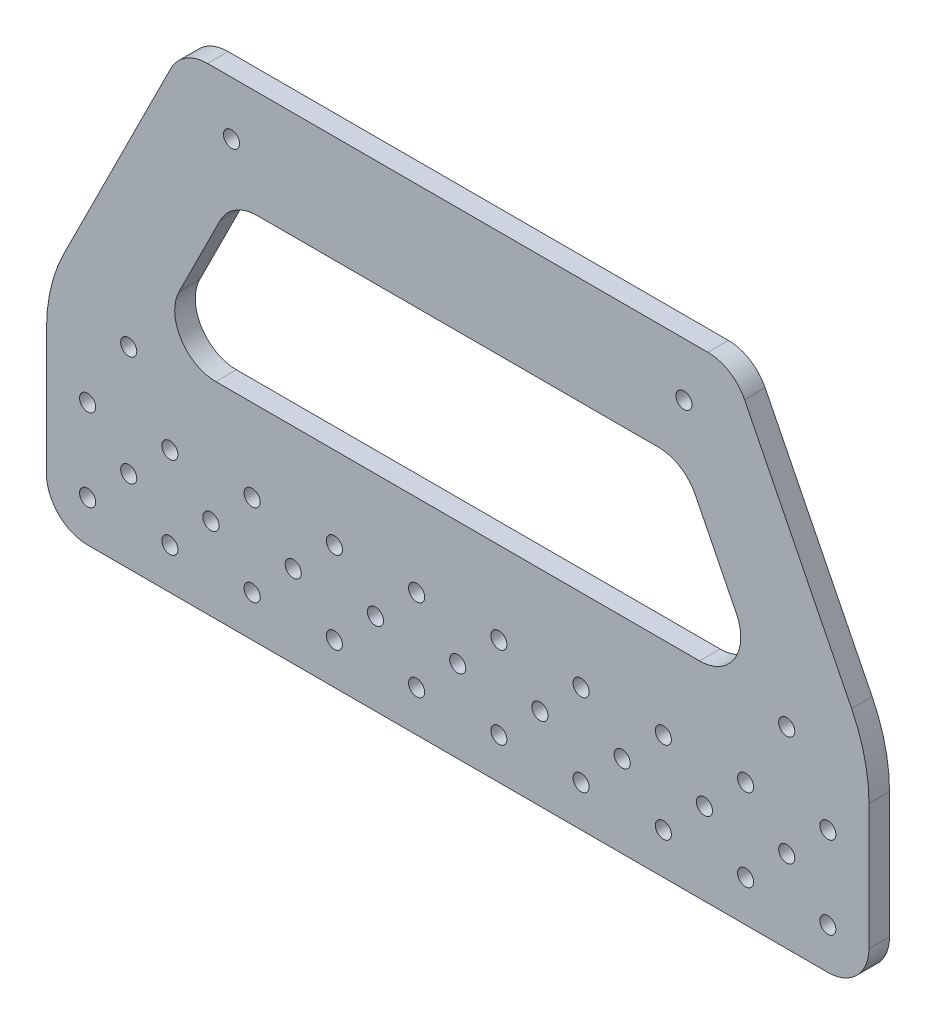
SolidWorks part; units mm, degrees
material "PC High Viscosity"
ref_plane "Front Plane" through (0, 0, 0) normal (0, 0, 1) x (1, 0, 0)
ref_plane "Top Plane" through (0, 0, 0) normal (0, 1, 0) x (1, 0, 0)
ref_plane "Right Plane" through (0, 0, 0) normal (1, 0, 0) x (0, 0, -1)
sketch "Sketch1" plane through (0, 0, 0) normal (0, 0, 1) x (1, 0, 0)
  line L0 (40.9398, 81.8796) -> (53.6398, 107.2796)
  line L1 (12.7, 0) -> (241.3, 0)
  line L2 (0, 12.7) -> (0, 51.5077)
  line L3 (52.299, 63.5) -> (201.701, 63.5)
  line L4 (254, 12.7) -> (254, 51.5077)
  line L5 (57.15, 63.5) -> (196.85, 63.5)
  line L6 (57.15, 63.5) -> (57.15, 114.3) construction
  line L7 (64.999, 114.3) -> (189.001, 114.3)
  line L8 (196.85, 63.5) -> (196.85, 114.3) construction
  line L9 (213.0602, 81.8796) -> (200.3602, 107.2796)
  line L10 (5.3631, 74.2262) -> (38.3998, 140.2996)
  line L11 (49.759, 147.32) -> (204.241, 147.32)
  line L12 (215.6002, 140.2996) -> (248.6369, 74.2262)
  line L13 (0, 63.5) -> (31.75, 63.5) construction
  line L14 (222.25, 63.5) -> (254, 63.5) construction
  arc A0 (204.241, 147.32) -> (215.6002, 140.2996) centre (204.241, 134.62) cw
  arc A1 (38.3998, 140.2996) -> (49.759, 147.32) centre (49.759, 134.62) cw
  arc A2 (189.001, 114.3) -> (200.3602, 107.2796) centre (189.001, 101.6) cw
  arc A3 (213.0602, 81.8796) -> (201.701, 63.5) centre (201.701, 76.2) cw
  arc A4 (40.9398, 81.8796) -> (52.299, 63.5) centre (52.299, 76.2) ccw
  arc A5 (53.6398, 107.2796) -> (64.999, 114.3) centre (64.999, 101.6) cw
  arc A6 (248.6369, 74.2262) -> (254, 51.5077) centre (203.2, 51.5077) cw
  arc A7 (0, 51.5077) -> (5.3631, 74.2262) centre (50.8, 51.5077) cw
  arc A8 (241.3, 0) -> (254, 12.7) centre (241.3, 12.7) ccw
  arc A9 (12.7, 0) -> (0, 12.7) centre (12.7, 12.7) cw
  point P40 (254, 0)
  point P43 (0, 0)
  dimension "D9" = 12.7
  dimension "D10" = 50.8
  dimension "D11" = 12.7
  dimension "D1" = 63.5
  dimension "D2" = 254
  dimension "D3" = 50.8
  dimension "D4" = 139.7
  dimension "D5" = 57.15
  dimension "D6" = 25.4
  dimension "D7" = 25.4
  dimension "D8" = 33.02
extrude "Boss-Extrude1" add sketch "Sketch1" along normal blind 6.35 contours A1 L10 L2 L1 L4 L12 A0 L11 L0 A5 L7 A2 L9 A3 L3 A4 region at (127, 62.9596, 0)
sketch "Sketch2" plane through (0, 0, 6.35) normal (0, 0, 1) x (1, 0, 0)
  line L0 (12.7, 0) -> (241.3, 0) construction
  line L1 (254, 12.7) -> (254, 51.5077) construction
  line L2 (241.3, 12.7) -> (215.9, 12.7) construction
  line L3 (241.3, 12.7) -> (241.3, 38.1) construction
  line L4 (25.4, 25.4) -> (50.8, 25.4) construction
  circle A0 centre (241.3, 12.7) radius 2.4892
  circle A1 centre (215.9, 12.7) radius 2.4892
  circle A2 centre (190.5, 12.7) radius 2.4892
  circle A3 centre (165.1, 12.7) radius 2.4892
  circle A4 centre (139.7, 12.7) radius 2.4892
  circle A5 centre (114.3, 12.7) radius 2.4892
  circle A6 centre (88.9, 12.7) radius 2.4892
  circle A7 centre (63.5, 12.7) radius 2.4892
  circle A8 centre (38.1, 12.7) radius 2.4892
  circle A9 centre (12.7, 12.7) radius 2.4892
  circle A10 centre (215.9, 38.1) radius 2.4892
  circle A11 centre (190.5, 38.1) radius 2.4892
  circle A12 centre (165.1, 38.1) radius 2.4892
  circle A13 centre (139.7, 38.1) radius 2.4892
  circle A14 centre (114.3, 38.1) radius 2.4892
  circle A15 centre (88.9, 38.1) radius 2.4892
  circle A16 centre (63.5, 38.1) radius 2.4892
  circle A17 centre (38.1, 38.1) radius 2.4892
  circle A18 centre (12.7, 38.1) radius 2.4892
  circle A19 centre (241.3, 38.1) radius 2.4892
  circle A20 centre (25.4, 25.4) radius 2.4892
  circle A21 centre (50.8, 25.4) radius 2.4892
  circle A22 centre (76.2, 25.4) radius 2.4892
  circle A23 centre (101.6, 25.4) radius 2.4892
  circle A24 centre (127, 25.4) radius 2.4892
  circle A25 centre (152.4, 25.4) radius 2.4892
  circle A26 centre (177.8, 25.4) radius 2.4892
  circle A27 centre (203.2, 25.4) radius 2.4892
  circle A28 centre (228.6, 25.4) radius 2.4892
  dimension "D1" = 4.9784
  dimension "D2" = 12.7
  dimension "D3" = 12.7
  dimension "D8" = 12.7
  dimension "D9" = 12.7
  dimension "D6" = 25.4
  dimension "D7" = 25.4
  dimension "D11" = 25.4
  dimension "D4" = 10
  dimension "D5" = 2
  dimension "D10" = 9
extrude "Cut-Extrude1" cut sketch "Sketch2" against normal through all
sketch "Sketch3" plane through (0, 0, 6.35) normal (0, 0, 1) x (1, 0, 0)
  line L0 (127, 0) -> (127, 147.32) construction
  line L1 (12.7, 0) -> (241.3, 0) construction
  line L2 (49.759, 147.32) -> (204.241, 147.32) construction
  line L3 (201.701, 76.2) -> (228.6, 59.3327) construction
  circle A0 centre (25.4, 59.3327) radius 2.4892
  circle A1 centre (57.15, 130.81) radius 2.4892
  circle A2 centre (196.85, 130.81) radius 2.4892
  circle A3 centre (228.6, 59.3327) radius 2.4892
  circle A4 centre (127, 130.81) radius 2.4892 construction
  arc A5 (201.701, 63.5) -> (213.0602, 81.8796) centre (201.701, 76.2) ccw construction
  arc A6 (201.701, 63.5) -> (213.0602, 81.8796) centre (201.701, 76.2) ccw
  dimension "D3" = 4.9784
  dimension "D4" = 101.6
  dimension "D5" = 101.6
  dimension "D7" = 16.51
  dimension "D1" = 69.85
  dimension "D2" = 69.85
  dimension "D6" = 31.75
extrude "Cut-Extrude2" cut sketch "Sketch3" against normal through all contours A1 | A4 | A2 | A3 | A0 region at (25.4, 59.3327, 6.35) region at (57.15, 130.81, 6.35) region at (196.85, 130.81, 6.35) region at (228.6, 59.3327, 6.35)
